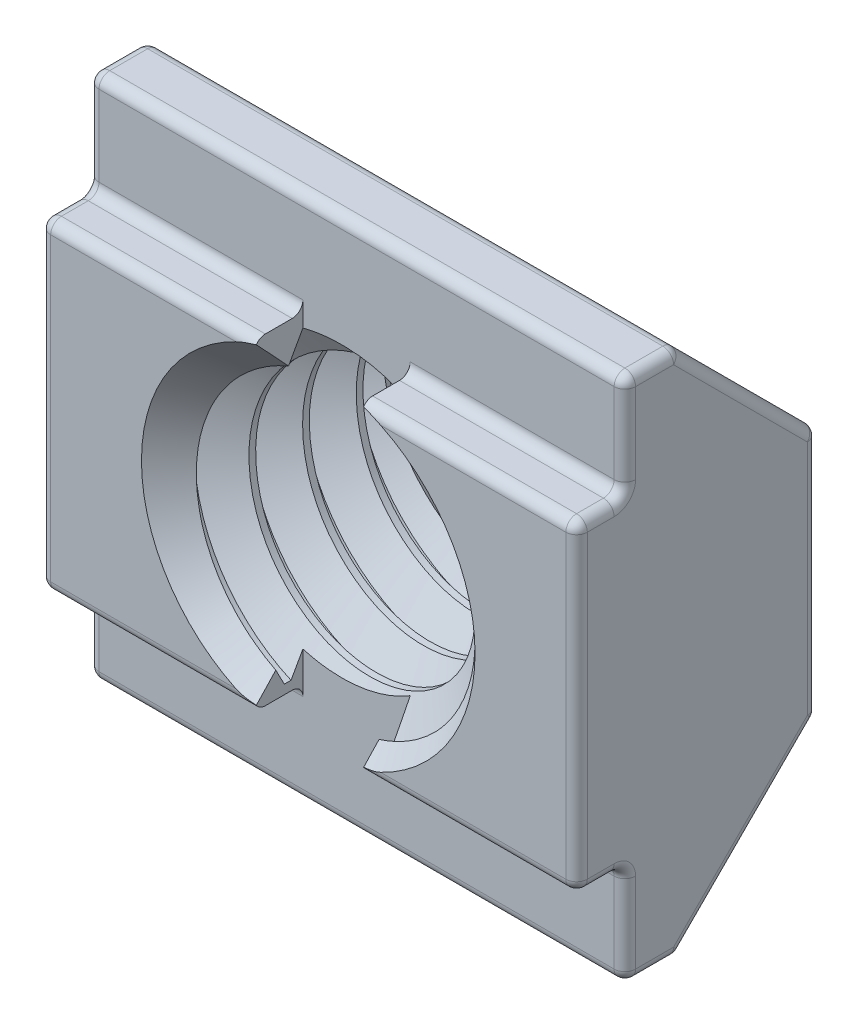
SolidWorks part; units mm, degrees
ref_plane "Front Plane" through (0, 0, 0) normal (0, 0, 1) x (1, 0, 0)
ref_plane "Top Plane" through (0, 0, 0) normal (0, 1, 0) x (1, 0, 0)
ref_plane "Right Plane" through (0, 0, 0) normal (1, 0, 0) x (0, 0, -1)
sketch "Sketch1" plane through (0, 0, 0) normal (0, 0, 1) x (1, 0, 0)
  line L0 (0, 4.9) -> (0, -4.9) construction
  line L1 (-5, 4.9) -> (5, 4.9) construction
  line L2 (-5, 4.9) -> (-5, -4.9) construction
  line L3 (-5, -4.9) -> (5, -4.9) construction
  line L4 (5, 4.9) -> (5, -4.9) construction
  line L5 (-5, 0) -> (5, 0) construction
  circle A1 centre (0, 0) radius 3 construction
  point P5 (0, 0)
  point P12 (0, -3)
  point P14 (0, 3)
  dimension "Thread Diameter" = 6
  dimension "Length" = 10
  dimension "Width" = 9.8
  dimension "D3" = 5
sketch "Sketch2" plane through (0, 0, 0) normal (1, 0, 0) x (0, 0, -1)
  line L0 (-2.25, 0) -> (2.25, 0) construction
  line L1 (-3.1875, 3.1083) -> (-2.6875, 2.2422)
  line L2 (-2.25, 3) -> (-2.25, -3) construction
  line L3 (-2.6875, 2.2422) -> (-2.1875, 3.1083)
  line L4 (-2.1875, 3.1083) -> (-3.1875, 3.1083)
  line L5 (-2.6875, 3.1083) -> (-2.6875, 3)
  line L6 (-2.6875, 2.2422) -> (-2.6875, 2.3505)
  line L7 (-3.125, 3) -> (-2.25, 3)
  line L8 (-3.1562, 3.0541) -> (-2.2188, 3.0541)
  line L9 (-2.75, 2.3505) -> (-2.625, 2.3505)
  point P3 (0, 0)
  point P6 (-2.25, 0)
  point P7 (-1.35, 0)
  point P9 (-2.25, -3)
  point P11 (-2.25, 3)
  point P22 (-2.6875, 3)
  point P25 (-2.6875, 3.0541)
  point P28 (-2.6875, 2.3505)
  dimension "D1" = 6
  dimension "D2" = 0.9
  dimension "Thickness" = 4.5
  dimension "Thread Pitch" = 1
  dimension "D6" = 0.125
sketch "Sketch3" plane through (0, 0, 0) normal (1, 0, 0) x (0, 0, -1)
  line L0 (-2.25, 3) -> (-1.35, 3)
  line L1 (-1.35, 3) -> (-1.35, 4.9)
  line L3 (-2.25, -3) -> (-1.35, -3)
  line L4 (-1.35, -3) -> (-1.35, -4.9)
  line L9 (-1.35, 4.9) -> (-0.36, 4.9)
  line L10 (-0.36, 4.9) -> (2.25, 2.29)
  line L11 (2.25, 2.29) -> (2.25, -2.29)
  line L12 (2.25, -2.29) -> (-0.36, -4.9)
  line L13 (-0.36, -4.9) -> (-1.35, -4.9)
  line L14 (-2.25, 3) -> (-2.25, -3)
  line L15 (-2.25, 0) -> (2.25, 0) construction
  point P16 (2.25, 0)
  dimension "D4" = 2.61
  dimension "D3" = 45
extrude "Boss-Extrude1" add sketch "Sketch3" against normal up to vertex (5 mm away) and the other way up to vertex (5 mm away) up to point (-5, 0, 0) other way up to point (5, 4.9, 0)
fillet "Fillet4" radius 0.2 10 edges at (0, -3, 2.25) (0, -3, 1.35) (0, -4.9, 1.35) (0, -4.9, 0.36) (0, -2.29, -2.25) (0, 2.29, -2.25) (0, 4.9, 0.36) (0, 4.9, 1.35) (0, 3, 1.35) (0, 3, 2.25)
sketch "Sketch19" plane through (0, 0, 2.25) normal (0, 0, 1) x (1, 0, 0)
  line L1 (-1, 4.9) -> (1, 4.9)
  line L2 (-1, 4.9) -> (-1, -4.9)
  line L3 (-1, -4.9) -> (1, -4.9)
  line L4 (1, 4.9) -> (1, -4.9)
  dimension "D1" = 2
extrude "Cut-Extrude11" cut sketch "Sketch19" against normal up to surface (0.9 mm away) up to face at (0, 3.95, 1.35)
sketch "Sketch6" plane through (0, 0, 2.25) normal (0, 0, 1) x (1, 0, 0)
  circle A0 centre (0, 0) radius 3 construction
  circle A1 centre (0, 0) radius 3
extrude "Cut-Extrude2" cut sketch "Sketch6" against normal through all
fillet "Fillet5" radius 0.2 40 edges at (-5, 2.9414, 2.1914) (-5, 3, 1.8) (-5, 3.0586, 1.4086) (-5, -3.95, 1.35) (-5, 4.8414, 1.2914) (-5, 4.9, 0.7964) (-5, 4.8848, 0.3663) (-5, 3.595, -0.945) (-5, 2.2837, -2.2348) (-5, 0, -2.25) (-5, -2.2837, -2.2348) (-5, -3.595, -0.945) (-5, -4.8848, 0.3663) (-5, -4.9, 0.7964) (-5, -4.8414, 1.2914) (-5, 3.95, 1.35) (-5, -3.0586, 1.4086) (-5, -3, 1.8) (-5, -2.9414, 2.1914) (5, 2.9414, 2.1914) (5, 3, 1.8) (5, 3.0586, 1.4086) (5, -3.95, 1.35) (5, 4.8414, 1.2914) (5, 4.9, 0.7964) (5, 4.8848, 0.3663) (5, 3.595, -0.945) (5, 2.2837, -2.2348) (5, 0, -2.25) (5, -2.2837, -2.2348) (5, -3.595, -0.945) (5, -4.8848, 0.3663) (5, -4.9, 0.7964) (5, -4.8414, 1.2914) (5, 3.95, 1.35) (5, -3.0586, 1.4086) (5, -3, 1.8) (5, -2.9414, 2.1914) (-5, 0, 2.25) (5, 0, 2.25)
sketch "Sketch8" plane through (0, 0, 0) normal (0, 0, 1) x (1, 0, 0)
  line L0 (0, 0) -> (2.1213, -2.1213)
  line L1 (-5, 0) -> (5, 0) construction
  circle A0 centre (0, 0) radius 3 construction
  circle A1 centre (0, 0) radius 3
  point P0 (-5, 4.9)
  point P1 (5, 4.9)
  point P3 (-5, -4.9)
  point P13 (2.1213, -2.1213)
  dimension "D1" = 45
sketch "Sketch9" plane through (0, 0, 0) normal (1, 0, 0) x (0, 0, -1)
  line L0 (2.25, 2.2072) -> (2.25, -2.2072) construction
  line L2 (2.25, 2.2072) -> (2.25, -2.2072)
  point P0 (-2.25, 3)
  point P1 (2.25, 2.2072)
  point P2 (-2.25, -3)
  point P7 (2.25, -2.2072)
ref_plane "Plane2" through (0, 0, 0) normal (1, 0, 0) x (0, 0, -1)
sketch "Sketch10" plane through (0, 0, 2.25) normal (0, 0, 1) x (1, 0, 0)
  circle A0 centre (0, 0) radius 3 construction
  circle A1 centre (0, 0) radius 3
curve "Helix/Spiral1" pitch 1 height 5.5 turns 5.5
sketch "Sketch11" plane through (0, 0, 0) normal (1, 0, 0) x (0, 0, -1)
  line L0 (-2.75, 2.3505) -> (-2.625, 2.3505) construction
  line L1 (-2.6875, 2.2422) -> (-2.1875, 3.1083) construction
  line L2 (-3.1875, 3.1083) -> (-2.6875, 2.2422) construction
  line L3 (-3.1562, 3.0541) -> (-2.2188, 3.0541) construction
  line L4 (-2.75, 2.3505) -> (-2.625, 2.3505)
  line L5 (-2.625, 2.3505) -> (-2.2188, 3.0541)
  line L6 (-3.1562, 3.0541) -> (-2.75, 2.3505)
  line L7 (-3.1562, 3.0541) -> (-2.2188, 3.0541)
sweep "Sweep1" add profiles "Sketch11" path "Helix/Spiral1"
sketch "Sketch20" plane through (0, 0, 2.25) normal (0, 0, 1) x (1, 0, 0)
  line L4 (1, 4.9) -> (-1, 4.9)
  line L5 (1, -4.9) -> (1, 4.9)
  line L6 (-1, -4.9) -> (1, -4.9)
  line L7 (-1, 4.9) -> (-1, -4.9)
  line L8 (1, 4.9) -> (-1, 4.9)
  line L9 (1, -4.9) -> (1, 4.9)
  line L10 (-1, -4.9) -> (1, -4.9)
  line L11 (-1, 4.9) -> (-1, -4.9)
  dimension "D1" = 0
extrude "Cut-Extrude12" cut sketch "Sketch20" against normal up to surface (0.9 mm away) and the other way through all up to face at (-0.0322, -3.5161, 1.35)
sketch "Sketch17" plane through (0, 0, 2.25) normal (0, 0, 1) x (1, 0, 0)
  circle A0 centre (0, 0) radius 3.1083
extrude "Cut-Extrude9" cut sketch "Sketch17" against normal through all draft 45 and the other way through all
sketch "Sketch18" plane through (0, 0, -2.25) normal (0, 0, -1) x (-1, 0, 0)
  circle A1 centre (0, 0) radius 3.1083
  circle A2 centre (0, 0) radius 3.1083
  dimension "D1" = 0
extrude "Cut-Extrude10" cut sketch "Sketch18" against normal through all draft 45 and the other way through all
sketch "Sketch21" plane through (5, 0, 0) normal (1, 0, 0) x (0, 0, -1)
  line L0 (-0.36, -4.9) -> (2.25, -4.9)
  line L1 (2.25, -4.9) -> (2.25, -2.29)
  line L2 (2.25, 2.29) -> (2.25, 4.9)
  line L3 (2.25, 4.9) -> (-0.36, 4.9)
  line L10 (-1.35, 4.9) -> (-1.35, 3)
  line L11 (-1.35, 3) -> (-2.25, 3)
  line L12 (-2.25, 3) -> (-2.25, -3)
  line L13 (-2.25, -3) -> (-1.35, -3)
  line L14 (-1.35, -3) -> (-1.35, -4.9)
  line L15 (-1.35, -4.9) -> (-0.36, -4.9)
  line L16 (-0.36, -4.9) -> (2.25, -2.29)
  line L17 (2.25, -2.29) -> (2.25, 2.29)
  line L18 (2.25, 2.29) -> (-0.36, 4.9)
  line L19 (-0.36, 4.9) -> (-1.35, 4.9)
  line L26 (-0.36, -4.9) -> (2.25, -2.29)
  line L28 (2.25, 2.29) -> (-0.36, 4.9)
  dimension "D1" = 0
extrude "Cut-Extrude13" cut sketch "Sketch21" against normal through all
equation "\"D6@Sketch2\" = \"Thread Pitch@Sketch2\" / 8"
equation "\"D3@Helix/Spiral1\" = \"Thickness@Sketch2\" + \"Thread Pitch@Sketch2\""
equation "\"D4@Helix/Spiral1\" = \"Thread Pitch@Sketch2\""
equation "\"D3@Sketch1\"=\"Length@Sketch1\"/2"
